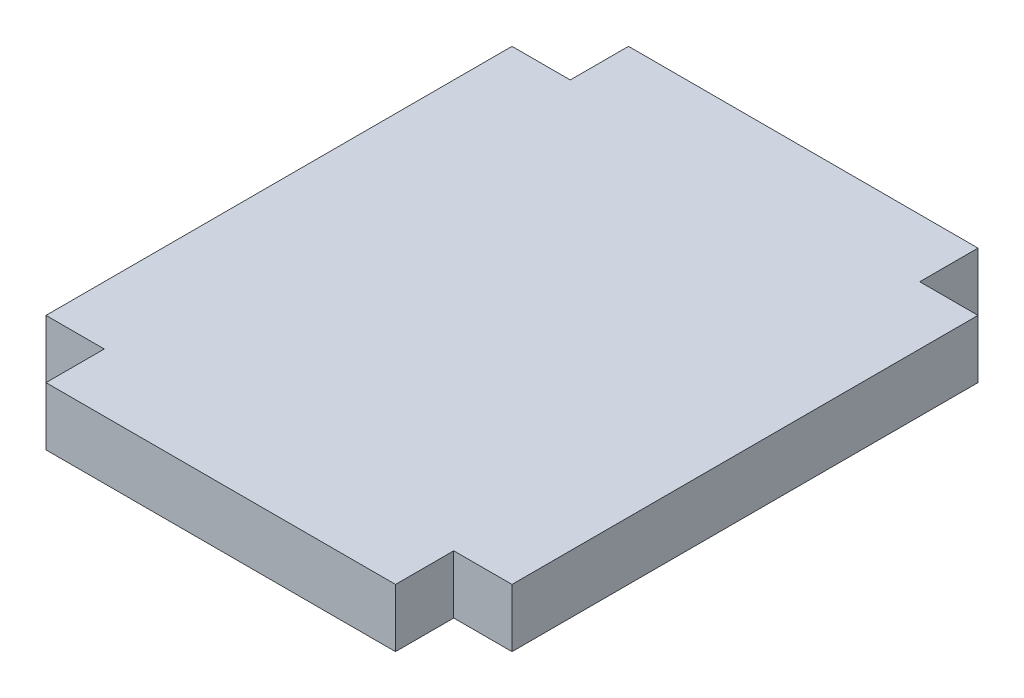
SolidWorks part; units mm, degrees
ref_plane "Alzado" through (0, 0, 0) normal (0, 0, 1) x (1, 0, 0)
ref_plane "Planta" through (0, 0, 0) normal (0, 1, 0) x (1, 0, 0)
ref_plane "Vista lateral" through (0, 0, 0) normal (1, 0, 0) x (0, 0, -1)
sketch "Croquis1" plane through (0, 0, 0) normal (0, 1, 0) x (1, 0, 0)
  line L0 (0, 0) -> (18, 0)
  line L1 (18, 0) -> (18, 3)
  line L2 (21, 3) -> (18, 3)
  line L3 (21, 3) -> (21, 27)
  line L4 (21, 27) -> (18, 27)
  line L5 (18, 27) -> (18, 30)
  line L6 (18, 30) -> (0, 30)
  line L8 (0, 27) -> (0, 30)
  line L9 (-3, 27) -> (0, 27)
  line L10 (-3, 3) -> (-3, 27)
  line L11 (0, 0) -> (0, 3)
  line L12 (18, 3) -> (18.0793, 3.0175)
  line L13 (0, 3) -> (-3, 3)
  point P13 (9, 30)
  dimension "D1" = 3
  dimension "D2" = 18
  dimension "D4" = 24
  dimension "D5" = 3
extrude "Saliente-Extruir1" add sketch "Croquis1" along normal blind 3 contours L13 L11 L0 L1 L2 L3 L4 L5 L6 L8 L9 L10 region at (9, 0, -15)
